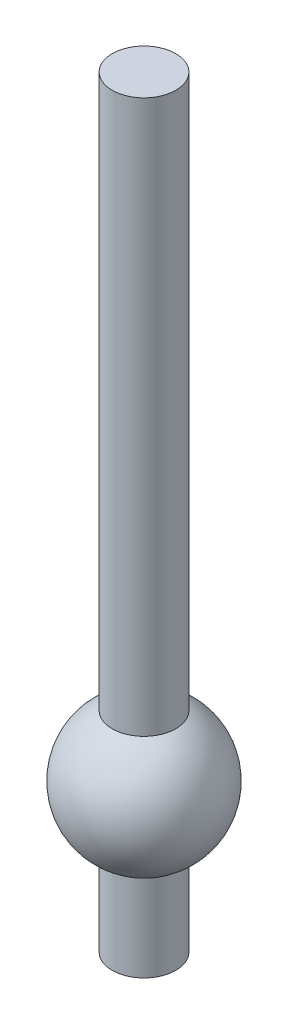
SolidWorks part; units mm, degrees
material "Plain Carbon Steel"
ref_plane "Front Plane" through (0, 0, 0) normal (0, 0, 1) x (1, 0, 0)
ref_plane "Top Plane" through (0, 0, 0) normal (0, 1, 0) x (1, 0, 0)
ref_plane "Right Plane" through (0, 0, 0) normal (1, 0, 0) x (0, 0, -1)
sketch "Sketch1" plane through (0, 0, 0) normal (0, 0, 1) x (1, 0, 0)
  line L0 (0, 0) -> (0, 72) construction
  line L1 (0, 0) -> (3, 0)
  line L2 (3, 0) -> (3, 8.2337)
  line L3 (3, 19.7663) -> (3, 72)
  line L4 (3, 72) -> (0, 72)
  line L5 (0, 72) -> (0, 0)
  arc A0 (3, 8.2337) -> (3, 19.7663) centre (0, 14) ccw
revolve "Revolve1" add sketch "Sketch1" angle 360 about L0
